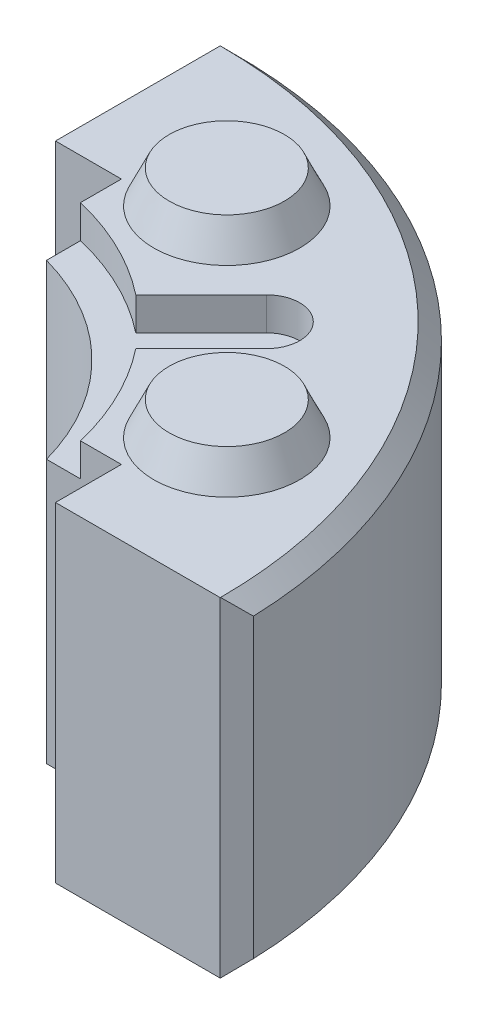
SolidWorks part; units mm, degrees
ref_plane "Front Plane" through (0, 0, 0) normal (0, 0, 1) x (1, 0, 0)
ref_plane "Top Plane" through (0, 0, 0) normal (0, 1, 0) x (1, 0, 0)
ref_plane "Right Plane" through (0, 0, 0) normal (1, 0, 0) x (0, 0, -1)
sketch "Sketch1" plane through (0, 0, 0) normal (0, 1, 0) x (1, 0, 0)
  line L0 (0, 0) -> (0, 50000) construction
  line L1 (0, 0) -> (-117661.3356, 0) construction
  line L2 (0, 150) -> (0, 75)
  line L3 (75, 0) -> (150, 0)
  arc A0 (150, 0) -> (0, 150) centre (0, 0) ccw
  arc A1 (75, 0) -> (0, 75) centre (0, 0) ccw
  arc A2 (112.5, 0) -> (0, 112.5) centre (0, 0) ccw construction
  dimension "D1" = 300
  dimension "D2" = 150
  dimension "D4" = 225
  dimension "D3" = 90
extrude "Boss-Extrude1" add sketch "Sketch1" along normal blind 100
ref_plane "Plane1" through (0, 110, 0) normal (0, 1, 0) x (1, 0, 0)
sketch "Sketch3" plane through (0, 110, 0) normal (0, 1, 0) x (1, 0, 0)
  line L0 (0, 0) -> (0, 50000) construction
  line L2 (0, 0) -> (50000, 0) construction
  line L3 (0, 0) -> (19134.1716, 46193.9766) construction
  arc A1 (112.5, 0) -> (0, 112.5) centre (0, 0) ccw construction
  circle A2 centre (43.0519, 103.9364) radius 17.5
  circle A3 centre (103.9364, 43.0519) radius 17.5
  circle A10 centre (-43.0519, 103.9364) radius 17.5 [skipped]
  circle A11 centre (-103.9364, 43.0519) radius 17.5 [skipped]
  circle A12 centre (-103.9364, -43.0519) radius 17.5 [skipped]
  arc A13 (-36.3549, -87.7686) -> (-49.7488, -120.1043) centre (-43.0519, -103.9364) ccw [skipped]
  circle A14 centre (43.0519, -103.9364) radius 17.5 [skipped]
  circle A15 centre (103.9364, -43.0519) radius 17.5 [skipped]
  point P29 (0, 0)
  dimension "D3" = 112.5
  dimension "D4" = 35
  dimension "D1" = 22.5
  dimension "D2" = 90
  dimension "D6" = 112.5
  dimension "D7" = 43.0519
  dimension "D5" = 8
extrude "Boss-Extrude3" add sketch "Sketch3" against normal blind 10 draft 25 draft outward yes
sketch "Sketch4" plane through (0, 0, 0) normal (0, -1, 0) x (1, 0, 0)
  line L0 (0, 0) -> (50000, 0) construction
  line L2 (0, 0) -> (0, -50000) construction
  line L3 (0, 0) -> (46193.9766, -19134.1716) construction
  arc A0 (0, -112.5) -> (112.5, 0) centre (0, 0) ccw construction
  circle A1 centre (103.9364, -43.0519) radius 18
  circle A2 centre (43.0519, -103.9364) radius 18
  circle A9 centre (-43.0519, 103.9364) radius 18 [skipped]
  circle A10 centre (43.0519, 103.9364) radius 18 [skipped]
  circle A11 centre (103.9364, 43.0519) radius 18 [skipped]
  arc A12 (-120.5663, 49.9402) -> (-87.3066, 36.1636) centre (-103.9364, 43.0519) ccw [skipped]
  circle A13 centre (-103.9364, -43.0519) radius 18 [skipped]
  circle A14 centre (-43.0519, -103.9364) radius 18 [skipped]
  point P13 (0, 0)
  point P28 (0, 0)
  dimension "D2" = 225
  dimension "D3" = 36
  dimension "D1" = 22.5
  dimension "D5" = 112.5
  dimension "D6" = 43.0519
  dimension "D4" = 8
extrude "Cut-Extrude1" cut sketch "Sketch4" against normal blind 11 draft 25
sketch "Sketch5" plane through (0, 0, 0) normal (0, -1, 0) x (1, 0, 0)
  line L0 (0, 0) -> (50000, 0) construction
  line L1 (-20, -55) -> (20, -55)
  line L2 (-20, -55) -> (-20, -95)
  line L3 (-20, -95) -> (20, -95)
  line L4 (20, -55) -> (20, -95)
  line L5 (-20, -55) -> (20, -95) construction
  line L6 (-20, -95) -> (20, -55) construction
  line L7 (0, 0) -> (35355.3391, -35355.3391) construction
  line L8 (95, 20) -> (95, -20)
  line L9 (55, -20) -> (95, -20)
  line L10 (55, 20) -> (55, -20)
  line L11 (55, 20) -> (95, 20)
  point P0 (0, -75)
  dimension "D1" = 40
  dimension "D2" = 40
  dimension "D3" = 45
extrude "Cut-Extrude2" cut sketch "Sketch5" against normal blind 144
chamfer "Chamfer1" distance 5 angle 45 4 edges at (150, 50, 0) (106.066, 100, -106.066) (0, 50, -150) (106.066, 0, -106.066)
sketch "Sketch6" plane through (0, 100, 0) normal (0, 1, 0) x (1, 0, 0)
  circle A0 centre (0, 0) radius 85
  dimension "D1" = 170
extrude "Cut-Extrude3" cut sketch "Sketch6" against normal blind 10
sketch "Sketch7" plane through (0, 0, 0) normal (0, -1, 0) x (1, 0, 0)
  circle A0 centre (0, 0) radius 85
  dimension "D1" = 170
extrude "Cut-Extrude4" cut sketch "Sketch7" against normal blind 10
sketch "Sketch8" plane through (0, 100, 0) normal (0, 1, 0) x (1, 0, 0)
  line L0 (0, 0) -> (0, 50000) construction
  line L1 (0, 0) -> (50000, 0) construction
  line L2 (-707.1068, -707.1068) -> (35355.3391, 35355.3391) construction
  line L7 (66.7577, 52.6156) -> (86.6206, 72.4784)
  line L8 (52.6156, 66.7577) -> (72.4784, 86.6206)
  arc A0 (112.5, 0) -> (0, 112.5) centre (0, 0) ccw construction
  arc A1 (86.6206, 72.4784) -> (72.4784, 86.6206) centre (79.5495, 79.5495) ccw
  arc A2 (66.7577, 52.6156) -> (52.6156, 66.7577) centre (0, 0) ccw
  dimension "D2" = 20
  dimension "D3" = 170
  dimension "D4" = 28.0903
  dimension "D1" = 45
  dimension "D5" = 10
  dimension "D6" = 20
extrude "Cut-Extrude5" cut sketch "Sketch8" against normal blind 10
sketch "Sketch10" plane through (0, 0, 0) normal (0, -1, 0) x (1, 0, 0)
  line L2 (86.6206, -72.4784) -> (66.7577, -52.6156)
  line L3 (52.6156, -66.7577) -> (72.4784, -86.6206)
  line L4 (86.6206, -72.4784) -> (66.7577, -52.6156)
  line L5 (52.6156, -66.7577) -> (72.4784, -86.6206)
  arc A2 (72.4784, -86.6206) -> (86.6206, -72.4784) centre (79.5495, -79.5495) ccw
  arc A3 (52.6156, -66.7577) -> (66.7577, -52.6156) centre (0, 0) ccw
  arc A4 (72.4784, -86.6206) -> (86.6206, -72.4784) centre (79.5495, -79.5495) ccw
  arc A5 (52.6156, -66.7577) -> (66.7577, -52.6156) centre (0, 0) ccw
  dimension "D1" = 0
extrude "Cut-Extrude6" cut sketch "Sketch10" against normal blind 10
